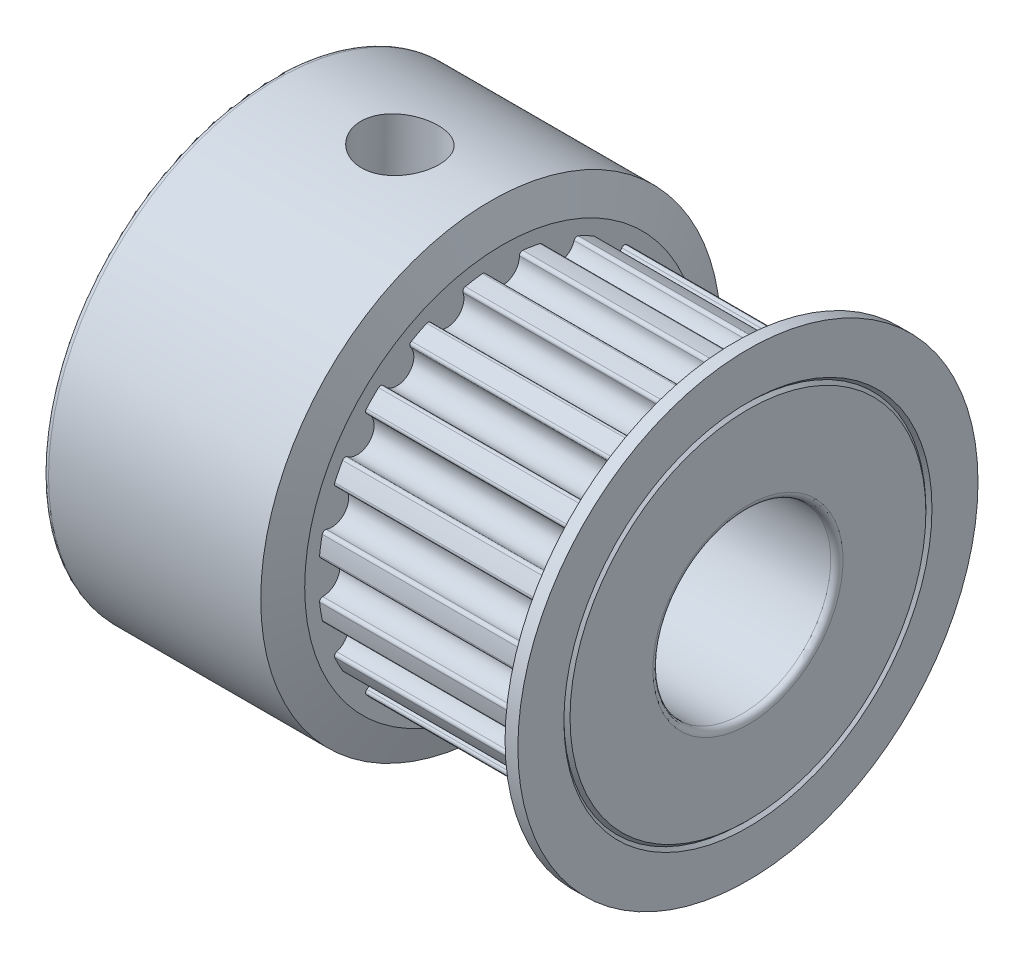
SolidWorks part; units mm, degrees
material "1.2311 (40CrMnMo7)"
ref_plane "Front" through (0, 0, 0) normal (0, 0, 1) x (1, 0, 0)
ref_plane "Top" through (0, 0, 0) normal (0, 1, 0) x (1, 0, 0)
ref_plane "Right" through (0, 0, 0) normal (1, 0, 0) x (0, 0, -1)
sketch "Sketch 1" plane through (0, 0, 0) normal (0, 0, 1) x (1, 0, 0)
  line L0 (-1.5, 2.9) -> (-1.5, 7.5)
  line L1 (1, 0) -> (14, 0) construction
  line L2 (-1.5, 7.5) -> (5.6176, 7.5)
  line L3 (5.6176, 7.5) -> (6, 6.4494)
  line L4 (6, 6) -> (13.2, 6)
  line L5 (13.2, 6) -> (13.2, 6.4494)
  line L6 (13.5824, 7.5) -> (14, 7.5)
  line L7 (14, 2.9) -> (14, 5.8)
  line L8 (14, 5.8) -> (13.9, 5.9)
  line L9 (13.9, 5.9) -> (14, 6)
  line L10 (14, 6) -> (14, 7.5)
  line L11 (14, 2.9) -> (-1.5, 2.9)
  line L12 (6, 6.4494) -> (6, 6)
  line L13 (13.2, 6.4494) -> (13.5824, 7.5)
  dimension "D1" = 7.5
  dimension "D2" = 20
  dimension "D3" = 2.9
  dimension "D5" = 0.1
  dimension "D8" = 7.2
revolve "Body" add sketch "Sketch 1" angle 360 about L1 region at (5.6242, 4.9083, 0)
sketch "Sketch 3" plane through (6, 0, 0) normal (1, 0, 0) x (0, 0, -1)
  line L0 (0, 0) -> (9.7637, 0) construction
  circle A18 centre (0, 5.855) radius 0.55
  point P45 (0, 0)
extrude "Cut-Extrude1" cut sketch "Sketch 3" along normal up to surface (7.2 mm away) up to face at (13.2, 0, 6.4494)
fillet "Fillet" radius 0.1 2 edges at (9.6, 5.976, -0.5365) (9.6, 5.976, 0.5365)
ref_axis "Axis1" through (0.35, 0, 0) along (1, 0, 0)
pattern_circular "CirPattern1" count 20 over 360 about axis through (0.35, 0, 0) along (1, 0, 0) of "Cut-Extrude1", "Fillet"
hole_wizard "M3 Tapped Hole1" positions "3DSketch1" profile "Sketch1" tap size "M3" standard "DIN"
sketch3d "3DSketch1"
  point P0 (2.5, 7.4984, -0.1544)
  dimension "D1" = 4
sketch "Sketch1" plane through (2.5, 7.4984, -0.1544) normal (1, 0, 0) x (0, 0.0206, 0.9998)
  line L0 (0, 0) -> (0, 8.2511)
  line L1 (0, 8.2511) -> (1.25, 7.5)
  line L2 (1.25, 7.5) -> (1.25, 0)
  line L5 (1.25, 0) -> (0, 0)
  line L10 (0, 8.2511) -> (-1.25, 7.5) construction
  line L11 (0, -6.35) -> (0, 107.95) construction
  dimension "Tap Drill Dia." = 2.5
  dimension "Tap Drill Depth" = 7.5
  dimension "Drill Angle" = 118
cosmetic thread "Hole Thread1" parameters "D1"=4.8832, "D2"=3
fillet "Fillet1" radius 0.2 4 edges at (14, 0, 2.9) (-1.5, 0, 2.9) (2.6689, 2.5962, -1.2922) (-1.5, 0, 7.5)
